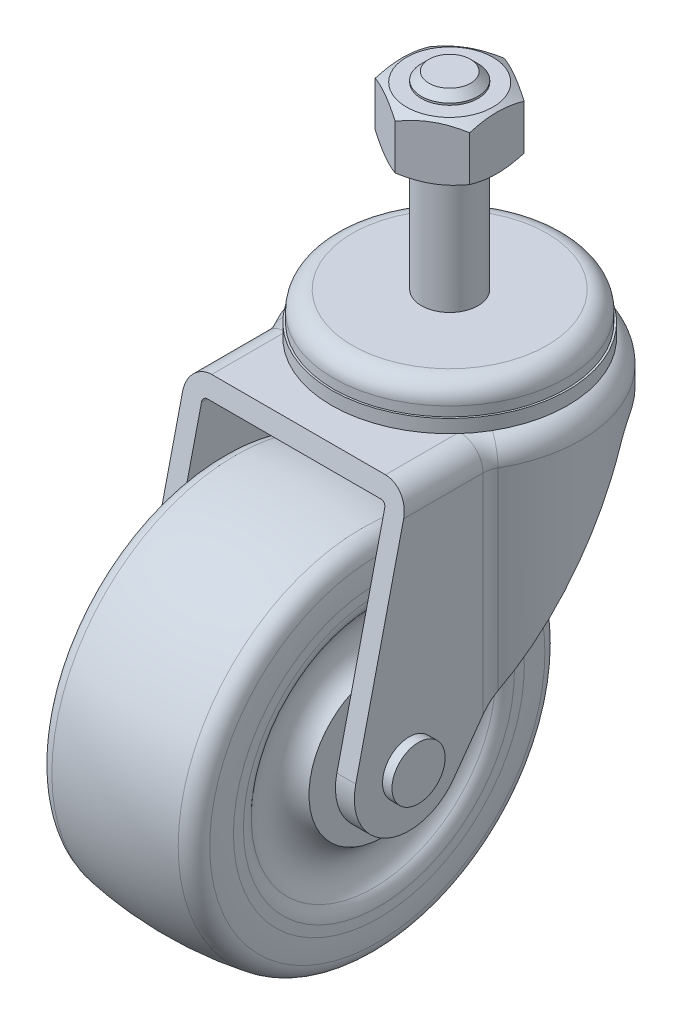
SolidWorks part; units mm, degrees
ref_plane "FRONT" through (0, 0, 0) normal (0, 0, 1) x (1, 0, 0)
ref_plane "TOP" through (0, 0, 0) normal (0, 1, 0) x (1, 0, 0)
ref_plane "RIGHT" through (0, 0, 0) normal (1, 0, 0) x (0, 0, -1)
sketch "Sketch1" plane through (0, 0, 0) normal (0, 1, 0) x (1, 0, 0)
  circle A0 centre (0, 0) radius 17.6276
  dimension "D1" = 35.2552
extrude "Base-Extrude" add sketch "Sketch1" against normal blind 33.02 from offset 5.588 offset against normal yes
sketch "Sketch2" plane through (0, 0, 0) normal (1, 0, 0) x (0, 0, -1)
  line L0 (-20.32, -5.588) -> (0, -5.588)
  line L1 (0, -38.608) -> (0, -5.588) construction
  line L2 (-20.32, -5.588) -> (-27.4945, -36.4311)
  line L3 (17.6276, -5.588) -> (-17.6276, -5.588) construction
  line L4 (-14.3438, -42.4061) -> (0, -22.499)
  line L5 (0, 0) -> (0, -122.9181) construction
  line L6 (50, 0) -> (-50, 0) construction
  line L7 (0, 50) -> (0, -50) construction
  line L8 (0, -5.588) -> (0, -22.499)
  line L9 (0, -22.499) -> (7.9756, -11.43) construction
  line L10 (7.9756, -11.43) -> (22.032, -11.43) construction
  line L11 (17.6276, -38.608) -> (17.6276, -5.588) construction
  arc A0 (-27.4945, -36.4311) -> (-14.3438, -42.4061) centre (-20.32, -38.1) ccw
  circle A1 centre (-20.32, -38.1) radius 25.4 construction
  dimension "D5" = 14.732
  dimension "D7" = 63.5
  dimension "D1" = 50.8
  dimension "D4" = 45.72
  dimension "D2" = 20.32
  dimension "D3" = 9.652
  dimension "D6" = 11.43
extrude "Boss-Extrude1" add sketch "Sketch2" along normal mid plane 29.718
sketch "Sketch3" plane through (0, 0, 0) normal (1, 0, 0) x (0, 0, -1)
  line L0 (-14.3438, -42.4061) -> (-9.4838, -35.6612) construction
  line L1 (-56.995, -101.6) -> (7.9756, -11.43)
  line L2 (38.1, -11.43) -> (38.1, -101.6)
  line L3 (-56.995, -101.6) -> (38.1, -101.6)
  line L4 (7.9756, -11.43) -> (22.032, -11.43) construction
  line L6 (7.9756, -11.43) -> (38.1, -11.43)
  dimension "D1" = 38.1
  dimension "D2" = 101.6
extrude "Cut-Extrude1" cut sketch "Sketch3" against normal mid plane 76.2
fillet "Fillet1" radius 3.175 5 edges at (0, -5.588, -17.6276) (-14.859, -5.588, 14.9019) (14.859, -5.588, 14.9019) (14.859, -20.6246, 9.4838) (-14.859, -20.6246, 9.4838)
fillet "Fillet2" radius 4.064 1 edges at (0, -11.43, -7.9756)
shell "Shell1" thickness 2.54 removed face at (0, -31.8078, 6.7073) removed face at (0, -42.1124, 22.143) removed face at (0, -16.7082, 22.9067) removed face at (0.1194, -12.103, -8.2886) removed face at (0, -11.43, -13.842)
ref_plane "Plane1" through (0, 0, 20.32) normal (0, 0, 1) x (1, 0, 0)
sketch "Sketch4" plane through (-12.319, 0, 0) normal (1, 0, 0) x (0, 0, -1)
  circle A0 centre (-20.32, -38.1) radius 3.175
  arc A3 (-27.4945, -36.4311) -> (-14.3438, -42.4061) centre (-20.32, -38.1) ccw construction
  dimension "D1" = 6.35
extrude "Boss-Extrude2" add sketch "Sketch4" along normal up to next
sketch "Sketch6" plane through (0, 0, 20.32) normal (0, 0, 1) x (1, 0, 0)
  line L1 (11.303, -41.275) -> (-11.303, -41.275)
  line L2 (-12.319, -41.275) -> (12.319, -41.275) construction
  line L3 (-10.795, -56.3205) -> (-10.795, -57.658)
  line L4 (0, -38.1) -> (-22.4069, -38.1) construction
  line L5 (12.319, -38.1) -> (-12.319, -38.1) construction
  line L6 (-12.319, -38.1) -> (-14.859, -38.1) construction
  line L7 (0, -38.1) -> (0, -63.5) construction
  line L8 (-11.303, -41.275) -> (-11.303, -48.006)
  line L9 (11.303, -41.275) -> (11.303, -48.006)
  line L10 (8.89, -46.6778) -> (8.89, -54.0284) construction
  line L12 (10.795, -56.3205) -> (10.795, -57.658)
  arc A0 (-8.4953, -62.7846) -> (8.4953, -62.7846) centre (0, -12.7) ccw
  arc A1 (11.303, -48.006) -> (10.0582, -54.5316) centre (12.917, -51.6954) ccw
  arc A2 (10.795, -57.658) -> (10.5856, -60.6359) centre (-10.4796, -57.658) cw
  arc A3 (10.0582, -54.5316) -> (10.795, -56.3205) centre (8.255, -56.3205) cw
  arc A4 (10.5856, -60.6359) -> (8.4953, -62.7846) centre (8.0706, -60.2804) cw
  arc A5 (-10.5856, -60.6359) -> (-8.4953, -62.7846) centre (-8.0706, -60.2804) ccw
  arc A6 (-10.795, -57.658) -> (-10.5856, -60.6359) centre (10.4796, -57.658) ccw
  arc A7 (-10.0582, -54.5316) -> (-10.795, -56.3205) centre (-8.255, -56.3205) ccw
  arc A8 (-11.303, -48.006) -> (-10.0582, -54.5316) centre (-12.917, -51.6954) cw
  point P19 (10.795, -55.118)
  point P22 (10.2469, -62.4558)
  point P24 (0, -63.5)
  point P37 (0, -41.275)
  dimension "D4" = 21.59
  dimension "D9" = 2.54
  dimension "D6" = 50.8
  dimension "D1" = 22.606
  dimension "D2" = 19.812
  dimension "D3" = 2.413
  dimension "D5" = 7.112
  dimension "D7" = 2.54
  dimension "D8" = 10.2469
revolve "Boss-Revolve1" add sketch "Sketch6" angle 360 about L4
sketch "Sketch8" plane through (0, 0, 0) normal (1, 0, 0) x (0, 0, -1)
  line L0 (0, 25.4) -> (0, -13.5012) construction
  line L1 (10.8363, -10.9612) -> (11.43, -10.9612)
  line L2 (3.81, 0) -> (13.081, 0)
  line L3 (14.4526, -5.588) -> (-7.2041, -5.588) construction
  line L4 (0, 25.4) -> (0, -13.5012)
  line L5 (15.621, -2.54) -> (15.621, -3.81)
  line L6 (0, -13.5012) -> (3.5645, -13.5012)
  line L7 (0, 25.4) -> (3.81, 25.4)
  line L8 (15.875, -3.81) -> (15.621, -3.81)
  line L9 (0, 0) -> (0, 58.0131) construction
  line L10 (3.81, 25.4) -> (3.81, 0)
  line L11 (15.875, -3.81) -> (15.875, -5.588)
  line L12 (50, 0) -> (-50, 0) construction
  line L13 (0, -11.43) -> (0, -8.763) construction
  line L14 (15.875, -5.588) -> (6.35, -5.588)
  line L15 (6.35, -5.588) -> (6.35, -10.9612)
  line L16 (11.43, -10.9612) -> (11.43, -13.5012)
  line L20 (6.35, -10.9612) -> (4.1581, -10.9612)
  arc A0 (15.621, -2.54) -> (13.081, 0) centre (13.081, -2.54) ccw
  arc A1 (3.5645, -13.5012) -> (11.43, -13.5012) centre (7.4972, -4.826) ccw
  arc A11 (4.1581, -10.9612) -> (10.8363, -10.9612) centre (7.4972, -4.826) ccw
  dimension "D6" = 39.751
  dimension "D8" = 9.525
  dimension "D2" = 2.54
  dimension "D3" = 0.254
  dimension "D4" = 25.4
  dimension "D5" = 7.62
  dimension "D7" = 22.86
  dimension "D9" = 5.3732
  dimension "D11" = 12.7
  dimension "D12" = 31.75
  dimension "D13" = 1.778
  dimension "D10" = 2.54
revolve "Boss-Revolve2" add sketch "Sketch8" angle 360 about L9
chamfer "Chamfer1" distance 1.016 angle 45 1 edges at (0, 25.4, -3.81)
sketch "Sketch9" plane through (0, 25.4, 0) normal (0, 1, 0) x (-1, 0, 0)
  line L1 (0, 7.3323) -> (-6.35, 3.6662)
  line L2 (-6.35, 3.6662) -> (-6.35, -3.6662)
  line L3 (-6.35, -3.6662) -> (0, -7.3323)
  line L4 (0, -7.3323) -> (6.35, -3.6662)
  line L5 (6.35, -3.6662) -> (6.35, 3.6662)
  line L6 (6.35, 3.6662) -> (0, 7.3323)
  circle A0 centre (0, 0) radius 6.35 construction
  circle A1 centre (0, 0) radius 3.81 construction
  circle A2 centre (0, 0) radius 3.81
  dimension "D1" = 12.7
extrude "Boss-Extrude3" add sketch "Sketch9" against normal blind 7.7978 from offset 1.27 offset against normal yes
sketch "Sketch10" plane through (0, 6.8128, 0.1695) normal (1, 0, 0) x (0, 0, -1)
  line L0 (0.1695, 0) -> (0.1695, 22.4951) construction
  line L3 (-8.6869, 9.5194) -> (-5.6389, 9.5194)
  line L5 (-8.6869, 17.3172) -> (-5.6389, 17.3172)
  line L7 (-7.1629, 16.4373) -> (-7.1629, 10.3992)
  line L8 (-8.6869, 17.3172) -> (-8.6869, 9.5194)
  line L9 (-5.6389, 17.3172) -> (-7.1629, 16.4373)
  line L10 (-5.6389, 9.5194) -> (-7.1629, 10.3992)
  line L11 (0.1695, 12.5775) -> (0.1695, -26.2032) construction
  line L12 (-7.1629, 9.5194) -> (-7.1629, 17.3172) construction
  line L13 (-7.1629, 13.4183) -> (-8.6869, 13.4183) construction
  line L14 (-7.1629, 17.3172) -> (-3.4967, 17.3172) construction
  dimension "D1" = 0.8799
  dimension "D2" = 1.524
  dimension "D3" = 1.524
revolve "Cut-Revolve1" cut sketch "Sketch10" angle 360 about L0
sketch "Sketch12" plane through (0, 0, 0) normal (1, 0, 0) x (0, 0, -1)
  circle A0 centre (-20.32, -38.1) radius 3.5736
extrude "Extrude1" add sketch "Sketch12" along normal mid plane 32.258
